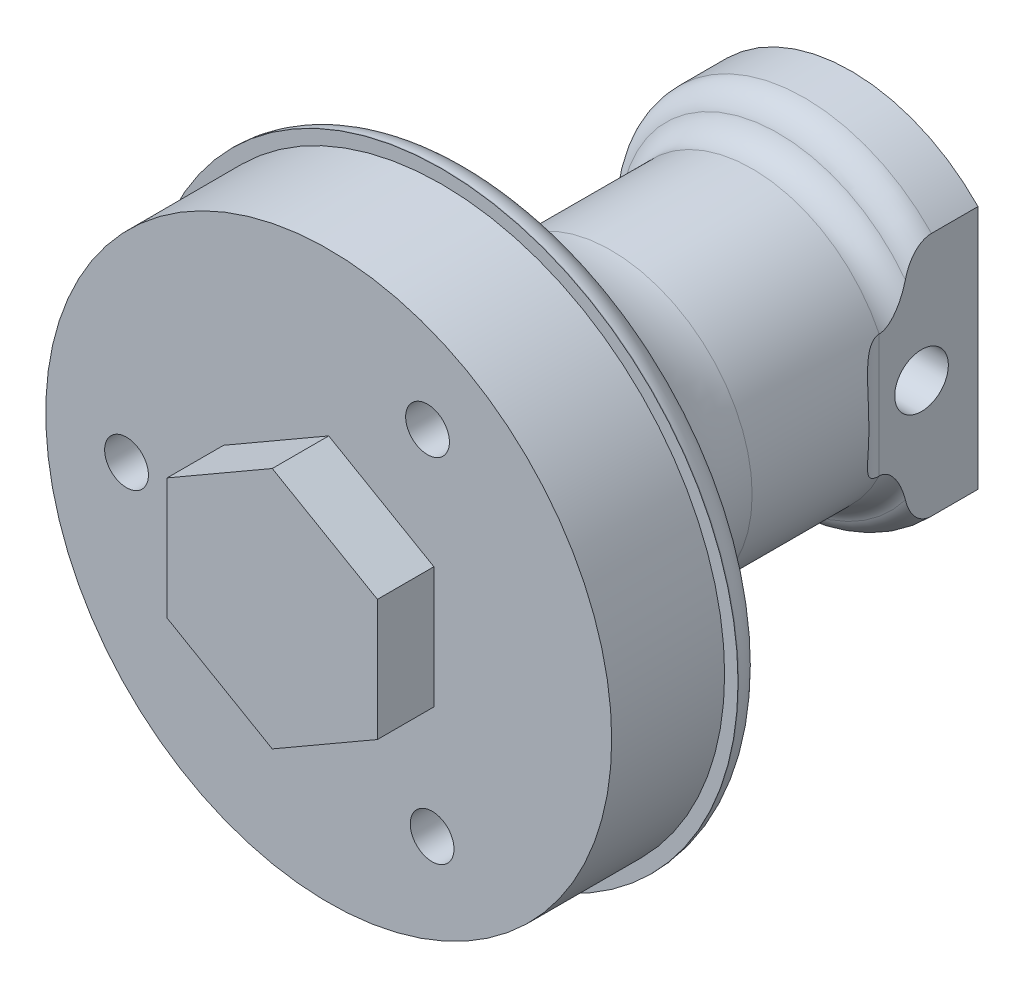
SolidWorks part; units mm, degrees
material "ABS"
ref_plane "Front Plane" through (0, 0, 0) normal (0, 0, 1) x (1, 0, 0)
ref_plane "Top Plane" through (0, 0, 0) normal (0, 1, 0) x (1, 0, 0)
ref_plane "Right Plane" through (0, 0, 0) normal (1, 0, 0) x (0, 0, -1)
sketch "Sketch1" plane through (0, 0, 0) normal (0, 0, 1) x (1, 0, 0)
  line L1 (0, 8.6025) -> (-7.45, 4.3013)
  line L2 (-7.45, 4.3013) -> (-7.45, -4.3013)
  line L3 (-7.45, -4.3013) -> (0, -8.6025)
  line L4 (0, -8.6025) -> (7.45, -4.3013)
  line L5 (7.45, -4.3013) -> (7.45, 4.3013)
  line L6 (7.45, 4.3013) -> (0, 8.6025)
  circle A0 centre (0, 0) radius 7.45 construction
  dimension "D1" = 14.9
extrude "Boss-Extrude1" add sketch "Sketch1" along normal blind 4
sketch "Sketch2" plane through (0, 0, 0) normal (0, 0, -1) x (-1, 0, 0)
  circle A0 centre (0, 0) radius 10
  dimension "D1" = 20
extrude "Boss-Extrude2" add sketch "Sketch2" along normal blind 37
ref_plane "Plane6" through (0, 0, 0) normal (0, 0, 1) x (1, 0, 0)
ref_plane "Plane4" through (0, 0, -33) normal (0, 0, -1) x (-1, 0, 0)
sketch "Sketch3" plane through (0, 0, -37) normal (0, 0, -1) x (-1, 0, 0)
  line L0 (0, 0) -> (0, 2.5) construction
  circle A1 centre (0, 0) radius 1.2
  dimension "D1" = 2.4
extrude "Cut-Extrude2" cut sketch "Sketch3" against normal blind 11
sketch "Sketch6" plane through (0, 0, 0) normal (0, 0, 1) x (1, 0, 0)
  circle A1 centre (0, 0) radius 20.05
  dimension "D1" = 40.1
extrude "Boss-Extrude4" add sketch "Sketch6" against normal blind 10
sketch "Sketch15" plane through (0, 0, -10) normal (0, 0, -1) x (-1, 0, 0)
  circle A0 centre (0, 0) radius 21
  dimension "D1" = 42
extrude "Boss-Extrude7" add sketch "Sketch15" against normal blind 2
sketch "Sketch7" plane through (0, 0, 0) normal (0, 0, 1) x (1, 0, 0)
  line L0 (0, 0) -> (0, 33.0451) construction
  circle A0 centre (7, 12.5) radius 1.55
  circle A1 centre (7.3253, -12.3122) radius 1.55
  circle A2 centre (-14.3253, -0.1878) radius 1.55
  point P11 (0, 0)
  dimension "D1" = 3.1
  dimension "D2" = 12.5
  dimension "D3" = 7
  dimension "D4" = 3
extrude "Cut-Extrude4" cut sketch "Sketch7" against normal up to next
sketch "Sketch10" plane through (0, 0, 0) normal (0, 1, 0) x (1, 0, 0)
  line L1 (0, 0) -> (0, 46.8839) construction
  line L3 (18, 10) -> (0, 10)
  line L5 (10, 28) -> (18, 10)
  line L6 (21, 10) -> (-21, 10) construction
  line L8 (10, 10) -> (10, 37) construction
  line L9 (10, 28) -> (0, 28)
  line L10 (0, 28) -> (0, 10)
  dimension "D1" = 18
  dimension "D3" = 18
ref_plane "Plane5" through (9, 0, 0) normal (1, 0, 0) x (0, 0, -1)
sketch "Sketch14" plane through (0, 0, -37) normal (0, 0, -1) x (-1, 0, 0)
  circle A1 centre (0, 0) radius 10
  circle A2 centre (0, 0) radius 10
  circle A3 centre (0, 0) radius 12.5
  dimension "D2" = 25
  dimension "D1" = 0
extrude "Boss-Extrude6" add sketch "Sketch14" against normal blind 5
sketch "Sketch12" plane through (9, 0, 0) normal (1, 0, 0) x (0, 0, -1)
  line L0 (37, -12.5) -> (37, 12.5) construction
  line L2 (0, 0) -> (12, 0) construction
  line L5 (28, 10) -> (28, -10)
  line L7 (10, -10) -> (32, -10) construction
  line L8 (32, 10) -> (10, 10) construction
  line L9 (28, -10) -> (37, -10)
  line L10 (37, 10) -> (28, 10)
  line L12 (37, -10) -> (37, 10)
extrude "Cut-Extrude5" cut sketch "Sketch12" along normal up to next
sketch "Sketch13" plane through (9, 0, 0) normal (1, 0, 0) x (0, 0, -1)
  line L0 (0, 0) -> (65.2829, 0) construction
  line L1 (0, -4.3013) -> (0, 4.3013) construction
  line L3 (28, 4.3589) -> (40.7641, -6.7686) construction
  line L5 (40.7641, -6.7686) -> (40.7641, 6.7686) construction
  line L6 (40.7641, 6.7686) -> (28, -4.3589) construction
  line L8 (28, 4.3589) -> (28, -4.3589)
  line L9 (28, -4.3589) -> (32, -4.3589)
  line L10 (37, -8.6747) -> (37, 8.6747)
  line L11 (32, 4.3589) -> (28, 4.3589)
  line L12 (28, 4.3589) -> (28, -4.3589) construction
  line L13 (28, -4.3589) -> (32, -4.3589) construction
  line L14 (37, -8.6747) -> (37, 8.6747) construction
  line L15 (32, 4.3589) -> (28, 4.3589) construction
  line L21 (32, -4.3589) -> (32, -8.6747)
  line L22 (32, -4.3589) -> (32, -8.6747)
  line L23 (32, -8.6747) -> (37, -8.6747)
  line L24 (32, -8.6747) -> (37, -8.6747)
  line L25 (37, 8.6747) -> (32, 8.6747)
  line L26 (37, 8.6747) -> (32, 8.6747)
  line L27 (32, 8.6747) -> (32, 4.3589)
  line L28 (32, 8.6747) -> (32, 4.3589)
  circle A1 centre (33, 0) radius 1.9
  dimension "D1" = 3.8
  dimension "D2" = 0
  dimension "D3" = 4
extrude "Cut-Extrude6" cut sketch "Sketch13" against normal mid plane 18 contours A1
revolve "Revolve1" [suppressed] add sketch "Sketch10" angle 360 about L1
sketch "Sketch16" [suppressed] plane through (0, 0, -10) normal (0, 0, -1) x (-1, 0, 0)
  line L0 (0, 0) -> (-7, 12.5) construction
  line L1 (-2.5496, 9.6695) -> (-4.0862, 17.5301)
  line L2 (-6.9121, 7.2265) -> (-12.8113, 12.644)
  arc A6 (-9, -4.3589) -> (-9, 4.3589) centre (0, 0) ccw construction
  arc A7 (-2.5496, 9.6695) -> (-6.9121, 7.2265) centre (0, 0) ccw
  circle A8 centre (0, 0) radius 18 construction
  arc A9 (-4.0862, 17.5301) -> (-12.8113, 12.644) centre (0, 0) ccw
  dimension "D1" = 5
  dimension "D2" = 10
extrude "Cut-Extrude7" [suppressed] cut sketch "Sketch16" along normal up to next
pattern_circular "CirPattern2" [suppressed] count 3 every 120 of bodies 122
fillet "Fillet1" radius 10 1 edges at (10, 0, -10)
fillet "Fillet2" radius 2 1 edges at (-21, 0, -10)
fillet "Fillet3" radius 2 1 edges at (-10, 0, -32)
fillet "Fillet4" radius 2 1 edges at (9, 0, -28)
fillet "Fillet5" radius 2 1 edges at (-12.5, 0, -32)
ref_plane "Plane7" through (0, 0, -10.5) normal (0, 0, 1) x (1, 0, 0)
sketch "Sketch17" plane through (0, 0, -10.5) normal (0, 0, 1) x (1, 0, 0)
  circle A0 centre (7, 12.5) radius 3
  circle A1 centre (7.3253, -12.3122) radius 3
  circle A2 centre (-14.3253, -0.1878) radius 3
  point P9 (0, 0)
  dimension "D1" = 6
  dimension "D2" = 3
extrude "Cut-Extrude8" cut sketch "Sketch17" against normal blind 10
